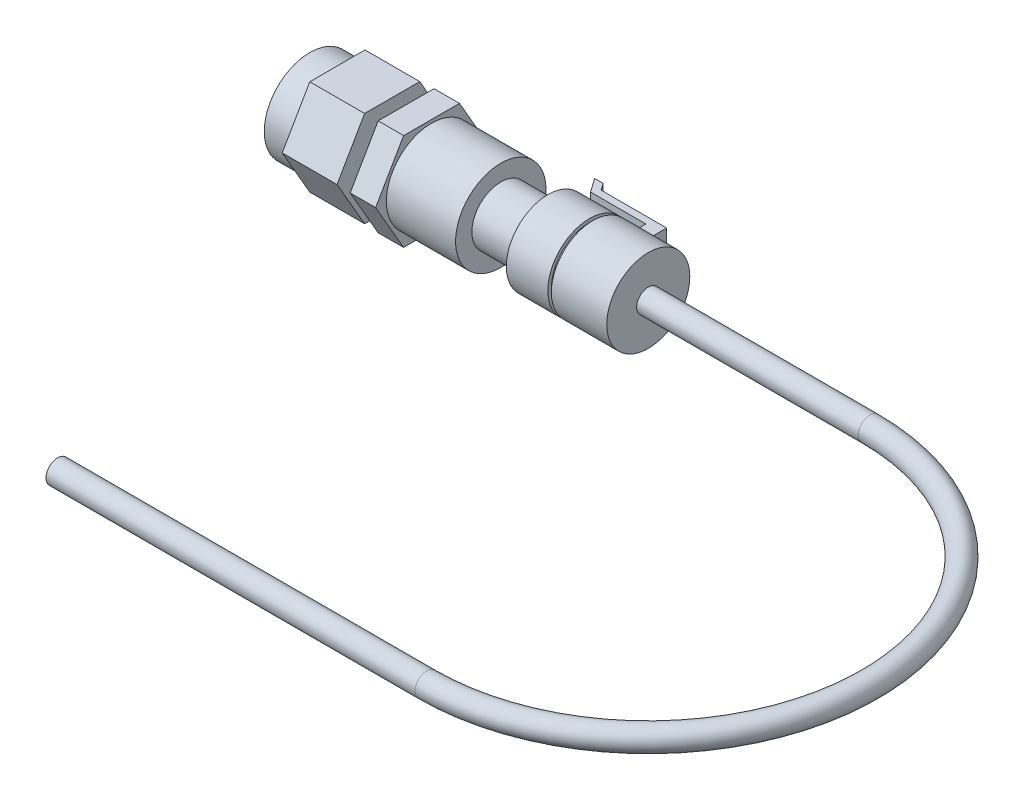
SolidWorks part; units mm, degrees
ref_plane "Front Plane" through (0, 0, 0) normal (0, 0, 1) x (1, 0, 0)
ref_plane "Top Plane" through (0, 0, 0) normal (0, 1, 0) x (1, 0, 0)
ref_plane "Right Plane" through (0, 0, 0) normal (1, 0, 0) x (0, 0, -1)
sketch "Sketch1" plane through (0, 0, 0) normal (1, 0, 0) x (0, 0, -1)
  circle A0 centre (0, 0) radius 10.3632
  dimension "D1" = 20.7264
extrude "Boss-Extrude1" add sketch "Sketch1" against normal blind 15.875
sketch "Sketch2" plane through (-15.875, 0, 0) normal (-1, 0, 0) x (0, 0, 1)
  line L1 (6.3973, 11.1062) -> (-6.4196, 11.0933)
  line L2 (-6.4196, 11.0933) -> (-12.8169, -0.0129)
  line L3 (-12.8169, -0.0129) -> (-6.3973, -11.1062)
  line L4 (-6.3973, -11.1062) -> (6.4196, -11.0933)
  line L5 (6.4196, -11.0933) -> (12.8169, 0.0129)
  line L6 (12.8169, 0.0129) -> (6.3973, 11.1062)
  circle A0 centre (0, 0) radius 11.0998 construction
  dimension "D1" = 22.1996
extrude "Boss-Extrude2" add sketch "Sketch2" along normal blind 5.842
sketch "Sketch3" plane through (-21.717, 0, 0) normal (-1, 0, 0) x (0, 0, 1)
  circle A0 centre (0, 0) radius 3.1314
extrude "Boss-Extrude3" add sketch "Sketch3" along normal blind 3.175
sketch "Sketch4" plane through (-24.892, 0, 0) normal (-1, 0, 0) x (0, 0, 1)
  line L1 (-12.6483, 0) -> (-6.3242, -10.9537)
  line L2 (-6.3242, -10.9537) -> (6.3242, -10.9537)
  line L3 (6.3242, -10.9537) -> (12.6483, 0)
  line L4 (12.6483, 0) -> (6.3242, 10.9538)
  line L5 (6.3242, 10.9538) -> (-6.3242, 10.9538)
  line L6 (-6.3242, 10.9538) -> (-12.6483, 0)
  circle A0 centre (0, 0) radius 10.9537 construction
  dimension "D1" = 21.9075
extrude "Boss-Extrude4" add sketch "Sketch4" along normal blind 12.573
sketch "Sketch5" plane through (-37.465, 0, 0) normal (-1, 0, 0) x (0, 0, 1)
  circle A0 centre (0, 0) radius 10.4775
  dimension "D1" = 20.955
extrude "Boss-Extrude5" add sketch "Sketch5" along normal blind 6.2865
sketch "Sketch6" plane through (0, 0, 0) normal (1, 0, 0) x (0, 0, -1)
  circle A0 centre (0, 0) radius 6.6357
  dimension "D1" = 13.2715
extrude "Boss-Extrude6" add sketch "Sketch6" along normal blind 10.795
sketch "Sketch7" plane through (10.795, 0, 0) normal (1, 0, 0) x (0, 0, -1)
  circle A0 centre (0, 0) radius 9.525
  dimension "D1" = 19.05
extrude "Boss-Extrude7" add sketch "Sketch7" along normal blind 9.525
sketch "Sketch9" plane through (20.32, 0, 0) normal (1, 0, 0) x (0, 0, -1)
  circle A0 centre (0, 0) radius 8.7376
  dimension "D1" = 17.4752
extrude "Boss-Extrude8" add sketch "Sketch9" along normal blind 0.7937
sketch "Sketch10" plane through (21.1137, 0, 0) normal (1, 0, 0) x (0, 0, -1)
  circle A0 centre (0, 0) radius 9.525
  dimension "D1" = 19.05
extrude "Boss-Extrude9" add sketch "Sketch10" along normal blind 12.7
ref_plane "Plane1" through (0, 0, -6.985) normal (0, 0, 1) x (1, 0, 0)
sketch "Sketch11" plane through (0, 0, -6.985) normal (0, 0, 1) x (1, 0, 0)
  line L0 (27.4637, 10.6143) -> (27.4637, -10.6143) construction
  line L1 (21.1137, 9.525) -> (21.1137, -9.525) construction
  line L2 (14.0986, 0) -> (-14.0986, 0) construction
  line L3 (27.4637, 5.8443) -> (27.4637, -5.8443)
  line L4 (27.4637, -5.8443) -> (20.32, -5.8443)
  line L5 (27.4637, 5.8443) -> (20.32, 5.8443)
  line L6 (20.32, -9.525) -> (20.32, 9.525) construction
  line L7 (20.32, -5.8443) -> (20.32, -1.4105)
  line L8 (20.32, -1.4105) -> (23.495, -1.4105)
  line L9 (23.495, -1.4105) -> (23.495, 1.4105)
  line L10 (20.32, 5.8443) -> (20.32, 1.4105)
  line L11 (20.32, 1.4105) -> (23.495, 1.4105)
  point P4 (27.4637, 0)
  point P16 (27.4637, 0)
  point P19 (23.495, 0)
  dimension "D1" = 6.35
  dimension "D2" = 7.1438
  dimension "D3" = 4.4337
  dimension "D4" = 3.175
extrude "Cut-Extrude1" cut sketch "Sketch11" along normal blind 1.5875
extrude "Cut-Extrude2" cut sketch "Sketch11<2>" against normal up to next
sketch "Sketch11<2>" plane through (0, 0, -6.985) normal (0, 0, 1) x (1, 0, 0) same geometry as "Sketch11"
sketch "Sketch12" plane through (0, 0, -5.3975) normal (0, 0, -1) x (-1, 0, 0)
  line L0 (-26.2857, -1.5875) -> (-26.2857, -4.7625)
  line L1 (-26.2857, -4.7625) -> (-23.1107, -4.7625)
  line L2 (-23.1107, -4.7625) -> (-23.1107, -1.5875)
  line L3 (-23.1107, -1.5875) -> (-26.2857, -1.5875)
  line L4 (14.0986, 0) -> (-14.0986, 0) construction
  line L5 (-23.1107, 4.7625) -> (-23.1107, 1.5875)
  line L6 (-26.2857, 4.7625) -> (-23.1107, 4.7625)
  line L7 (-26.2857, 1.5875) -> (-26.2857, 4.7625)
  line L8 (-23.1107, 1.5875) -> (-26.2857, 1.5875)
  point P3 (-26.2857, -3.175)
  dimension "D1" = 3.175
  dimension "D2" = 3.175
extrude "Boss-Extrude10" add sketch "Sketch12" along normal blind 6.35
sketch "Sketch13" plane through (23.1107, 0, 0) normal (-1, 0, 0) x (0, 0, 1)
  line L1 (-11.7475, -4.7625) -> (-10.16, -4.7625)
  line L2 (-11.7475, -4.7625) -> (-11.7475, -1.5875)
  line L3 (-11.7475, -1.5875) -> (-10.16, -1.5875)
  line L4 (-10.16, -4.7625) -> (-10.16, -1.5875)
  line L7 (14.0986, 0) -> (-14.0986, 0) construction
  line L8 (-11.7475, 1.5875) -> (-10.16, 1.5875)
  line L9 (-10.16, 4.7625) -> (-10.16, 1.5875)
  line L10 (-11.7475, 4.7625) -> (-10.16, 4.7625)
  line L11 (-11.7475, 4.7625) -> (-11.7475, 1.5875)
  dimension "D1" = 1.5875
extrude "Boss-Extrude11" add sketch "Sketch13" along normal blind 12.7
sketch "Sketch14" plane through (0, -4.7625, 0) normal (0, -1, 0) x (1, 0, 0)
  line L0 (12.3642, -10.16) -> (10.141, -13.335)
  line L1 (10.4107, -10.16) -> (23.1107, -10.16) construction
  line L2 (10.4107, -10.16) -> (8.1875, -13.335)
  line L3 (10.141, -13.335) -> (8.1875, -13.335)
  line L4 (12.3642, -10.16) -> (10.4107, -10.16)
  dimension "D1" = 55
  dimension "D2" = 3.175
  dimension "D3" = 1.6002
  dimension "D4" = 0
sketch "Sketch16" plane through (0, 4.7625, 0) normal (0, 1, 0) x (1, 0, 0)
  line L0 (10.4107, 10.16) -> (8.1875, 13.335) construction
  line L1 (10.141, 13.335) -> (8.1875, 13.335) construction
  line L2 (12.3642, 10.16) -> (10.141, 13.335) construction
  line L3 (10.4107, 10.16) -> (8.1875, 13.335)
  line L4 (10.141, 13.335) -> (8.1875, 13.335)
  line L5 (12.3642, 10.16) -> (10.141, 13.335)
  line L6 (12.3642, 10.16) -> (10.4107, 10.16)
extrude "Boss-Extrude12" add sketch "Sketch14" against normal blind 3.175
extrude "Boss-Extrude13" add sketch "Sketch16" against normal blind 3.175
sketch "Sketch17" plane through (0, 0, -13.335) normal (0, 0, -1) x (-1, 0, 0)
  line L0 (-10.141, 4.7625) -> (-8.1875, 4.7625)
  line L1 (-8.1875, 4.7625) -> (-8.1875, -4.7625)
  line L2 (-8.1875, -4.7625) -> (-10.141, -4.7625)
  line L3 (-10.141, -4.7625) -> (-10.141, 4.7625)
extrude "Boss-Extrude14" add sketch "Sketch17" against normal blind 1.5875
sketch "Sketch18" plane through (0, 4.7625, 0) normal (0, 1, 0) x (1, 0, 0)
  line L0 (12.5002, 10.16) -> (6.4013, 10.16) construction
  line L1 (10.4107, 10.16) -> (23.1107, 10.16) construction
  line L2 (10.4107, 10.16) -> (8.1875, 13.335)
  line L3 (8.1875, 13.335) -> (8.1875, 10.16)
  line L4 (8.1875, 10.16) -> (10.4107, 10.16)
  line L5 (8.1875, 11.7475) -> (8.1875, 13.335) construction
  dimension "D1" = 55
extrude "Cut-Extrude3" cut sketch "Sketch18" against normal up to next
sketch "Sketch19" plane through (0, 0, 0) normal (0, 1, 0) x (1, 0, 0)
  line L0 (33.8137, 0) -> (84.6137, 0)
  line L1 (33.8137, -9.525) -> (33.8137, 9.525) construction
  line L2 (84.6137, -101.6) -> (0, -101.6)
  line L3 (0, -12.2169) -> (0, 12.2169) construction
  arc A0 (84.6137, 0) -> (84.6137, -101.6) centre (84.6137, -50.8) cw
  point P7 (0, 0)
  dimension "D2" = 50.8
  dimension "D3" = 50.8
sketch "Sketch21" plane through (0, 0, 0) normal (1, 0, 0) x (0, 0, -1)
  line L0 (0, 0) -> (-101.6, 0) construction
  line L1 (63.2142, 0) -> (-63.2142, 0) construction
  circle A0 centre (-101.6, 0) radius 2.667
  dimension "D1" = 5.334
sweep "Sweep1" add profiles "Sketch21" path "Sketch19"
sketch "Sketch22" plane through (-43.7515, 0, 0) normal (-1, 0, 0) x (0, 0, 1)
  circle A0 centre (0, 0) radius 2.54
  circle A1 centre (0, 0) radius 10.4775 construction
  point P2 (0, 0)
  dimension "D1" = 5.08
extrude "Cut-Extrude4" cut sketch "Sketch22" against normal blind 27.94
